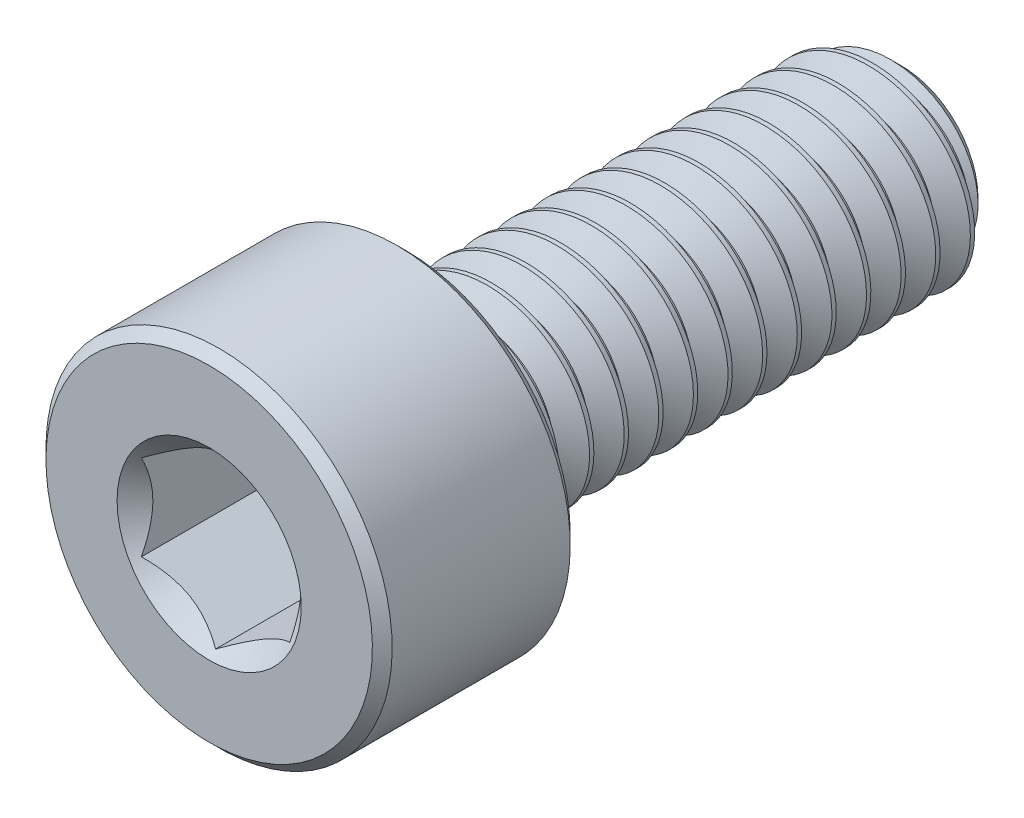
SolidWorks part; units mm, degrees
ref_plane "Front Plane" through (0, 0, 0) normal (0, 0, 1) x (1, 0, 0)
ref_plane "Top Plane" through (0, 0, 0) normal (0, 1, 0) x (1, 0, 0)
ref_plane "Right Plane" through (0, 0, 0) normal (1, 0, 0) x (0, 0, -1)
sketch "Sketch1" plane through (0, 0, 0) normal (1, 0, 0) x (0, 0, -1)
  line L0 (-7, 0) -> (7, 0) construction
  line L1 (7, 0) -> (7, 1.5453) construction
  line L2 (7, 1.5453) -> (6.5453, 2) construction
  line L3 (6.5453, 2) -> (6.475, 2) construction
  line L4 (6.475, 2) -> (-3, 2) construction
  line L5 (-3, 2) -> (-3, 3.5) construction
  line L6 (-3, 3.5) -> (-7, 3.5) construction
  line L7 (-7, 3.5) -> (-7, 0) construction
  line L8 (7, 1.5453) -> (7, 2) construction
  line L9 (6.9563, 2.0758) -> (7.3063, 1.4696) construction
  line L10 (7.3063, 1.4696) -> (7.6563, 2.0758) construction
  line L11 (7.6563, 2.0758) -> (6.9563, 2.0758) construction
  line L12 (7.3063, 2.0758) -> (7.3063, 2) construction
  line L13 (7.3063, 1.4696) -> (7.3063, 1.5453) construction
  line L14 (7.2625, 1.5453) -> (7.35, 1.5453) construction
  line L15 (7, 2) -> (7.6125, 2) construction
  line L16 (6.9781, 2.0379) -> (7.6344, 2.0379) construction
  line L17 (7, 0) -> (7, -2) construction
  line L18 (-3.2, 3.5) -> (-3, 3.3) construction
  line L19 (-6.8, 3.5) -> (-7, 3.3) construction
  line L20 (-3, 2) -> (-3, 0) construction
  line L21 (-3, 1) -> (0.3333, 1) construction
  line L22 (0.3333, 1) -> (3.6667, 1) construction
  line L23 (3.6667, 1) -> (7, 1) construction
  line L24 (0.3333, 1) -> (0.3333, 2) construction
  line L25 (0.3333, 2) -> (0.3333, 3.5) construction
  line L26 (3.6667, 1) -> (3.6667, 3.5) construction
  point P0 (-7, 1.5)
  point P3 (5.25, 2)
  point P4 (0, 0)
  point P18 (3.6667, 2)
  point P22 (7.3063, 1.5453)
  point P24 (6.475, 2)
  point P25 (7.3063, 2)
  point P28 (7.3063, 2.0379)
  point P29 (5.25, -2)
  point P30 (0.3333, 2)
  point P31 (-5, 3.5)
  point P37 (-3.7, 3.5)
  point P38 (-6.7, 3.5)
  point P45 (0.3333, 1)
  point P46 (3.6667, 1)
  dimension "D2" = 0.0875
  dimension "D7" = 0.2
  dimension "D8" = 0.2
  dimension "D9" = 0.2
  dimension "D10" = 0.1
  dimension "D11" = 0.5
  dimension "Drive Size" = 3
  dimension "Head Diameter" = 7
  dimension "Head Height" = 4
  dimension "Thread Pitch" = 0.7
  dimension "Thread Dia" = 4
  dimension "Length" = 10
  dimension "D12" = 0.525
  dimension "D4" = 1.75
  dimension "D3" = 45
sketch "Sketch2" plane through (0, 0, 0) normal (1, 0, 0) x (0, 0, -1)
  line L0 (-7, 0) -> (-7, 3.3)
  line L1 (-6.8, 3.5) -> (-3.2, 3.5)
  line L2 (-3, 3.3) -> (-3, 2.2)
  line L4 (6.5453, 2) -> (7, 1.5453)
  line L5 (7, 1.5453) -> (7, 0)
  line L6 (-3, 3.5) -> (-7, 3.5) construction
  line L7 (7, 0) -> (-7, 0)
  line L8 (-6.8, 3.5) -> (-7, 3.3) construction
  line L10 (-6.8, 3.5) -> (-7, 3.3)
  line L14 (-3.2, 3.5) -> (-3, 3.3) construction
  line L16 (-3.2, 3.5) -> (-3, 3.3)
  line L17 (-3, 2) -> (-3, 3.5) construction
  line L19 (-2.8, 2) -> (6.5453, 2)
  line L20 (6.475, 2) -> (-3, 2) construction
  arc A1 (-3, 2.2) -> (-2.8, 2) centre (-2.8, 2.2) ccw
  dimension "D3" = 0.2
revolve "Revolve1" add sketch "Sketch2" angle 360 about L7
sketch "Sketch3" plane through (0, 0, 7) normal (0, 0, 1) x (1, 0, 0)
  line L1 (1.5, -0.866) -> (1.5, 0.866)
  line L2 (1.5, 0.866) -> (0, 1.7321)
  line L3 (0, 1.7321) -> (-1.5, 0.866)
  line L4 (-1.5, 0.866) -> (-1.5, -0.866)
  line L5 (-1.5, -0.866) -> (0, -1.7321)
  line L6 (0, -1.7321) -> (1.5, -0.866)
  circle A0 centre (0, 0) radius 1.5 construction
  circle A1 centre (0, 0) radius 3.5 construction
  circle A2 centre (0, 0) radius 3.5 construction
  circle A3 centre (0, 0) radius 1.7321 construction
  point P13 (0, 0)
  dimension "D1" = 3.4641
extrude "Cut-Extrude1" cut sketch "Sketch3" against normal offset from surface (3 mm away) 1 up to face at (0, 3.3, 3)
sketch "Sketch4" plane through (0, 0, 7) normal (0, 0, 1) x (1, 0, 0)
  circle A0 centre (0, 0) radius 1.862
  dimension "D1" = 3.7239
extrude "Cut-Extrude2" cut sketch "Sketch4" against normal up to vertex (2 mm away) draft 45 up to point (0, 3.5, 5)
sketch "Sketch11" plane through (0, 0, 0) normal (1, 0, 0) x (0, 0, -1)
  line L0 (-7, 0) -> (7, 0) construction
  line L1 (-7, 0) -> (7, 0) construction
  line L2 (-1.125, 0) -> (-1.125, 2) construction
  line L3 (6.475, 2) -> (-3, 2) construction
  line L4 (5.125, 0) -> (5.125, 2) construction
  line L6 (7, 1.5453) -> (7, 2) construction
  point P2 (-1.125, 0)
  point P3 (5.125, 0)
  dimension "D1" = 1.875
  dimension "D2" = 1.875
sketch "Sketch6" plane through (0, 0, -7) normal (0, 0, -1) x (-1, 0, 0)
  circle A0 centre (0, 0) radius 2
curve "Helix/Spiral1" pitch 0.7 height 10.7 turns 15.2857
sketch "Sketch10" plane through (0, 0, 0) normal (1, 0, 0) x (0, 0, -1)
  line L0 (-2.8, -3.5) -> (-2.8, 3.5)
  line L5 (-7, 0) -> (7, 0) construction
  line L6 (-2.8, 2) -> (-2.8, -2) construction
  point P3 (-2.8, 0)
split "Split1" trim tools "Sketch10" bodies to split 106 resulting bodies 114 115
sketch "Sketch7" plane through (0, 0, 0) normal (1, 0, 0) x (0, 0, -1)
  line L0 (6.9781, 2.0379) -> (7.6344, 2.0379)
  line L1 (7.6344, 2.0379) -> (7.35, 1.5453)
  line L2 (7.35, 1.5453) -> (7.2625, 1.5453)
  line L3 (7.2625, 1.5453) -> (6.9781, 2.0379)
sweep "Cut-Sweep1" cut profiles "Sketch7" path "Helix/Spiral1" align with end faces yes
sketch "Sketch8" plane through (0, 0, 0) normal (1, 0, 0) x (0, 0, -1)
  line L0 (-3, 0) -> (-3, 2)
  line L1 (-2.8, -2) -> (-2.8, 2) construction
  line L2 (-3, 2) -> (-2.8, 2)
  line L4 (-2.8, 2) -> (-1.6453, 0)
  line L5 (-1.6453, 0) -> (-3, 0)
  line L6 (6.475, 2) -> (-3, 2) construction
  line L7 (-7, 0) -> (7, 0) construction
  dimension "D1" = 60
revolve "Revolve2" add sketch "Sketch8" angle 360 about L5
equation "\"D2@Sketch1\" = \"Thread Pitch@Sketch1\" / 8"
equation "\"D4@Helix/Spiral1\" = \"Thread Pitch@Sketch1\""
equation "\"D7@Sketch1\" = \"Head Height@Sketch1\" * .05"
equation "\"D8@Sketch1\"=\"D7@Sketch1\""
equation "\"D9@Sketch1\"=\"D7@Sketch1\""
equation "\"D10@Sketch1\"=\"D7@Sketch1\"/2"
equation "\"D11@Sketch1\"=\"D10@Sketch1\"*5"
equation "\"D4@Sketch1\"=\"Thread Pitch@Sketch1\"*2.5"
equation "\"D12@Sketch1\"=\"Thread Pitch@Sketch1\"*.75"
equation "\"D3@Helix/Spiral1\"=\"Length@Sketch1\"+\"Thread Pitch@Sketch1\""
equation "\"D3@Sketch2\"=\"Thread Dia@Sketch1\"*0.05"
equation "\"D1@Sketch11\"=\"Length@Sketch1\"*0.1875"
equation "\"D2@Sketch11\"=\"D1@Sketch11\""
equation "\"D1@Sketch4\"=\"D1@Sketch3\"*1.075"
